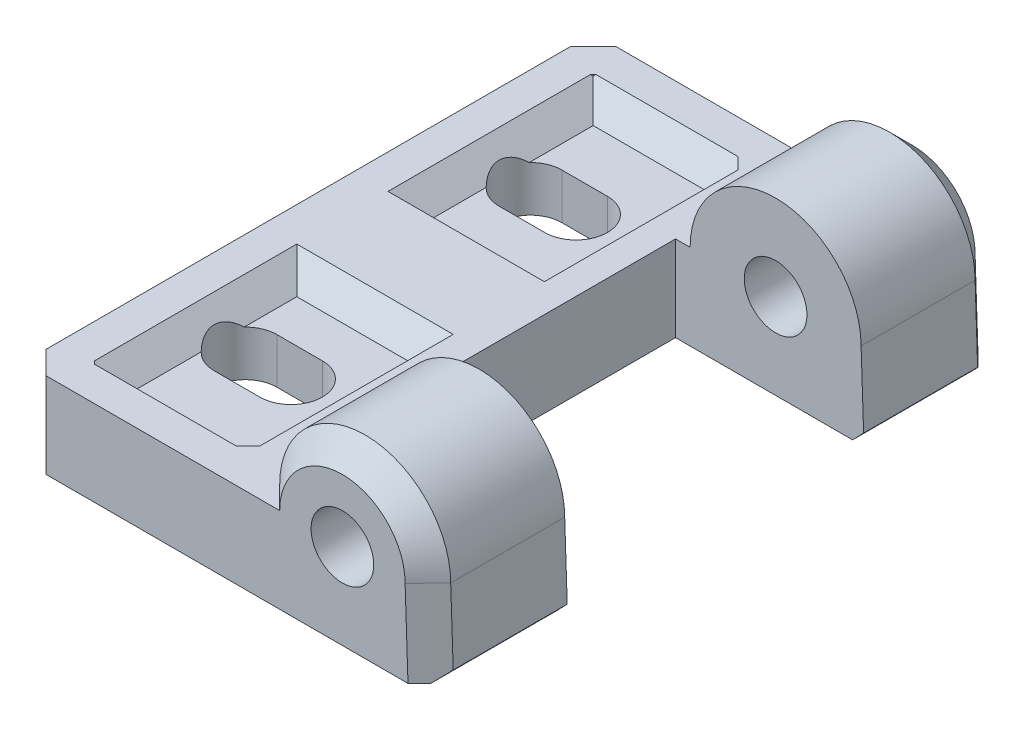
SolidWorks part; units mm, degrees
ref_plane "Front Plane" through (0, 0, 0) normal (0, 0, 1) x (1, 0, 0)
ref_plane "Top Plane" through (0, 0, 0) normal (0, 1, 0) x (1, 0, 0)
ref_plane "Right Plane" through (0, 0, 0) normal (1, 0, 0) x (0, 0, -1)
sketch "contour" plane through (0, 0, 0) normal (0, 0, 1) x (1, 0, 0)
  line L0 (7.5, 0) -> (7.7213, -6.5006)
  line L1 (-7.5, -0.0001) -> (-28, -0.0001)
  line L2 (6.7554, -7.5) -> (0, -7.5)
  line L3 (0, -7.5) -> (-28, -7.5)
  line L4 (-28, -0.0001) -> (-28, -7.5)
  line L5 (7.7213, -6.5006) -> (6.7554, -7.5)
  arc A0 (7.5, 0) -> (-7.5, -0.0001) centre (0, 0) ccw
  point P6 (7.7554, -7.5)
  dimension "D2" = 15
  dimension "D3" = 28
extrude "Boss-Extrude1" add sketch "contour" along normal mid plane 50
sketch "Sketch6" plane through (0, -7.5, 0) normal (0, -1, 0) x (1, 0, 0)
  line L0 (-28, 25) -> (-28, -25) construction
  line L1 (-28, 25) -> (6.7554, 25) construction
  line L2 (-21, 12.5) -> (-17, 12.5) construction
  line L3 (-21, 15.25) -> (-17, 15.25)
  line L4 (-21, 9.75) -> (-17, 9.75)
  line L5 (-21, -12.5) -> (-17, -12.5) construction
  line L6 (-21, -9.75) -> (-17, -9.75)
  line L7 (-21, -15.25) -> (-17, -15.25)
  circle A0 centre (-19, 12.5) radius 2.75 construction
  circle A1 centre (-19, -12.5) radius 2.75 construction
  arc A2 (-21, 15.25) -> (-21, 9.75) centre (-21, 12.5) ccw
  arc A3 (-17, 9.75) -> (-17, 15.25) centre (-17, 12.5) ccw
  arc A4 (-21, -9.75) -> (-21, -15.25) centre (-21, -12.5) ccw
  arc A5 (-17, -15.25) -> (-17, -9.75) centre (-17, -12.5) ccw
  point P10 (-19, 12.5)
  point P16 (-19, -12.5)
  dimension "D1" = 5.5
  dimension "D2" = 9
  dimension "D5" = 4
  dimension "D3" = 12.5
  dimension "D4" = 25
extrude "mount-holes" cut sketch "Sketch6" against normal through all
sketch "Sketch7" plane through (0, -7.5, 0) normal (0, -1, 0) x (1, 0, 0)
  line L1 (7.7213, 13) -> (-8.7787, 13)
  line L2 (7.7213, 13) -> (7.7213, -13)
  line L3 (7.7213, -13) -> (-8.7787, -13)
  line L4 (-8.7787, 13) -> (-8.7787, -13)
  line L5 (-7.5, -25) -> (7.5, -25) construction
  line L6 (7.5, 25) -> (-7.5, 25) construction
  line L7 (7.7213, 25) -> (7.7213, -25) construction
  dimension "D1" = 12
  dimension "D2" = 12
  dimension "D3" = 16.5
extrude "cut-part" cut sketch "Sketch7" against normal blind 20
sketch "axis" plane through (0, 0, 0) normal (0, 0, 1) x (1, 0, 0)
  circle A0 centre (0, 0) radius 2.75
  dimension "D1" = 5.5
extrude "Cut-Extrude3" cut sketch "axis" against normal mid plane 60
sketch "Sketch9" plane through (0, -7.5, 0) normal (0, -1, 0) x (1, 0, 0)
  line L17 (-17, 18.75) -> (-21, 18.75)
  line L18 (-21, 6.25) -> (-17, 6.25)
  line L19 (-17, 18.75) -> (-21, 18.75)
  line L20 (-21, 6.25) -> (-17, 6.25)
  line L23 (-21, -18.75) -> (-17, -18.75)
  line L24 (-17, -6.25) -> (-21, -6.25)
  line L25 (-21, -18.75) -> (-17, -18.75)
  line L26 (-17, -6.25) -> (-21, -6.25)
  arc A8 (-21, 18.75) -> (-21, 6.25) centre (-21, 12.5) ccw
  arc A9 (-17, 6.25) -> (-17, 18.75) centre (-17, 12.5) ccw
  arc A10 (-21, 18.75) -> (-21, 6.25) centre (-21, 12.5) ccw
  arc A11 (-17, 6.25) -> (-17, 18.75) centre (-17, 12.5) ccw
  arc A14 (-21, -6.25) -> (-21, -18.75) centre (-21, -12.5) ccw
  arc A15 (-17, -18.75) -> (-17, -6.25) centre (-17, -12.5) ccw
  arc A16 (-21, -6.25) -> (-21, -18.75) centre (-21, -12.5) ccw
  arc A17 (-17, -18.75) -> (-17, -6.25) centre (-17, -12.5) ccw
  dimension "D1" = 3.5
  dimension "D2" = 3.5
extrude "Cut-Extrude4" cut sketch "Sketch9" against normal blind 1.5
chamfer "Chamfer1" distance 2 angle 45 6 edges at (7.6107, -3.2503, -25) (7.6107, -3.2503, 25) (-28, -3.75, -25) (-28, -3.75, 25) (0, 7.5, -25) (0, 7.5, 25)
sketch "Sketch10" plane through (0, -0.0001, 0) normal (0, 1, 0) x (1, 0, 0)
  line L0 (-11.2787, 0) -> (-25, 0) construction
  line L1 (-11.2787, 4) -> (-25, 4)
  line L2 (-11.2787, -4) -> (-25, -4)
  line L3 (-25, -4) -> (-25, -21.7574)
  line L4 (-11.2787, -4) -> (-11.2787, -21)
  line L12 (-11.2787, 21) -> (-11.2787, 4)
  line L13 (-12.2787, 22) -> (-11.2787, 21)
  line L14 (-11.2787, -21) -> (-12.2787, -22)
  line L34 (-12.2787, 22) -> (-24.7574, 22)
  line L35 (-24.7574, 22) -> (-25, 21.7574)
  line L36 (-25, 21.7574) -> (-25, 4)
  line L37 (-25, -21.7574) -> (-24.7574, -22)
  line L38 (-24.7574, -22) -> (-12.2787, -22)
  point P0 (-11.2787, 22)
  point P4 (-11.2787, -22)
  dimension "D1" = 4
  dimension "D2" = 4
extrude "Cut-Extrude5" cut sketch "Sketch10" against normal blind 2
chamfer "Chamfer2" distance 2 angle 45 8 edges at (-18.518, -2.0001, 22) (-25, -2.0001, -12.8787) (-18.518, -2.0001, -22) (-11.2787, -2.0001, -12.5) (-18.1393, -2.0001, -4) (-25, -2.0001, 12.8787) (-18.1393, -2.0001, 4) (-11.2787, -2.0001, 12.5)
